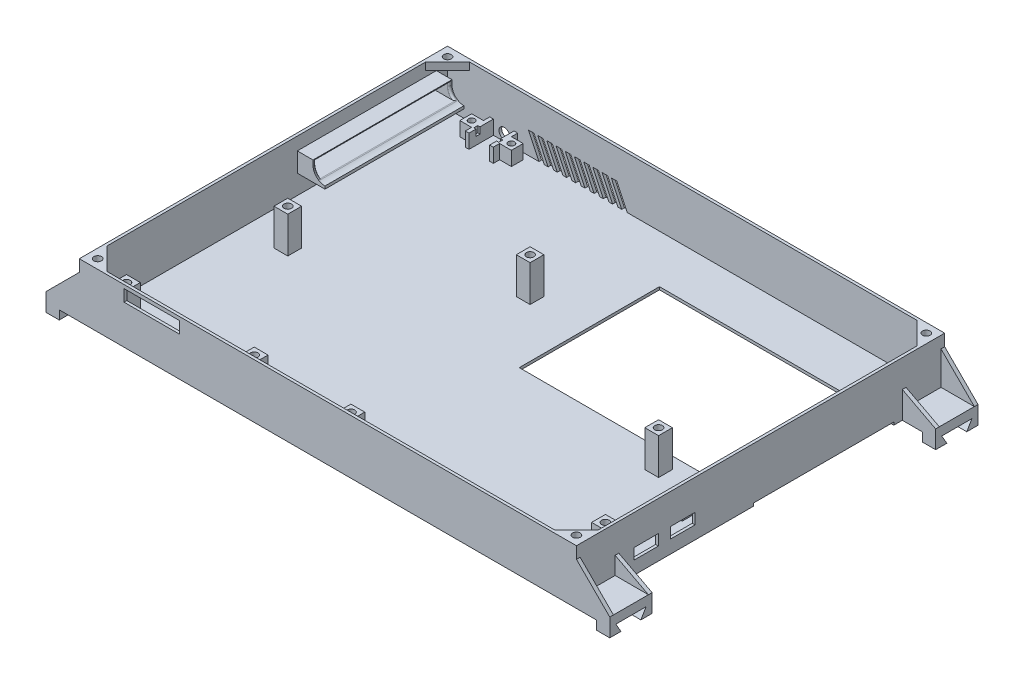
SolidWorks part; units mm, degrees
material "PLA"
ref_plane "Спереди" through (0, 0, 0) normal (0, 0, 1) x (1, 0, 0)
ref_plane "Сверху" through (0, 0, 0) normal (0, 1, 0) x (1, 0, 0)
ref_plane "Справа" through (0, 0, 0) normal (1, 0, 0) x (0, 0, -1)
sketch "Эскиз1" plane through (0, 0, 0) normal (0, 1, 0) x (1, 0, 0)
  line L1 (135, 100) -> (-135, 100)
  line L2 (135, 100) -> (135, -100)
  line L3 (135, -100) -> (-135, -100)
  line L4 (-135, 100) -> (-135, -100)
  line L5 (135, 100) -> (-135, -100) construction
  line L6 (135, -100) -> (-135, 100) construction
  point P0 (0, 0)
  dimension "D1" = 200
  dimension "D2" = 270
extrude "Бобышка-Вытянуть1" add sketch "Эскиз1" along normal blind 1.5
sketch "Эскиз2" plane through (0, 1.5, 0) normal (0, 1, 0) x (1, 0, 0)
  line L0 (133.5, 98.5) -> (-133.5, 98.5)
  line L1 (-133.5, 98.5) -> (-133.5, -98.5)
  line L2 (-133.5, -98.5) -> (-110.7, -98.5)
  line L3 (133.5, -98.5) -> (133.5, 98.5)
  line L4 (-135, 100) -> (-135, -100)
  line L5 (-135, -100) -> (135, -100)
  line L6 (135, -100) -> (135, 100)
  line L7 (135, 100) -> (-135, 100)
  line L8 (-135, 100) -> (-135, -100)
  line L9 (-135, -100) -> (-110.7, -100)
  line L10 (135, -100) -> (135, 100)
  line L11 (135, 100) -> (-135, 100)
  line L12 (-110.7, -98.5) -> (-110.7, -100)
  line L14 (-80.5, -98.5) -> (-80.5, -100)
  line L16 (-80.5, -98.5) -> (133.5, -98.5)
  line L17 (-80.5, -100) -> (135, -100)
  line L18 (-133.5, -98.5) -> (133.5, -98.5) construction
  line L20 (-135, -100) -> (135, -100) construction
  dimension "D3" = 24.3
  dimension "D4" = 54.5
  dimension "D1" = 0
  dimension "D2" = 1.5
extrude "Бобышка-Вытянуть2" add sketch "Эскиз2" along normal offset from surface (28 mm away) 7 offset beyond the face yes
sketch "Эскиз3" plane through (0, 1.5, 0) normal (0, 1, 0) x (1, 0, 0)
  line L1 (-110.7, -98.5) -> (-80.5, -98.5)
  line L2 (-110.7, -98.5) -> (-110.7, -100)
  line L3 (-110.7, -100) -> (-80.5, -100)
  line L4 (-80.5, -98.5) -> (-80.5, -100)
extrude "Бобышка-Вытянуть3" add sketch "Эскиз3" along normal blind 19.7
sketch "Эскиз4" plane through (-110.7, 0, 0) normal (1, 0, 0) x (0, 0, -1)
  line L0 (-100, 29.5) -> (-100, 21.2) construction
  line L1 (-98.5, 29.5) -> (-100, 29.5)
  line L2 (-98.5, 29.5) -> (-98.5, 27.6)
  line L3 (-98.5, 27.6) -> (-100, 27.6)
  line L4 (-100, 29.5) -> (-100, 27.6)
  dimension "D1" = 1.9
extrude "Бобышка-Вытянуть4" add sketch "Эскиз4" along normal up to surface (30.2 mm away) up to face at (-80.5, 25.35, 99.25)
sketch "Эскиз5" plane through (135, 0, 0) normal (1, 0, 0) x (0, 0, -1)
  line L0 (-100, 29.5) -> (-100, 0) construction
  line L1 (-55.55, 13) -> (-68.85, 13)
  line L2 (-55.55, 13) -> (-55.55, 7.1)
  line L3 (-55.55, 7.1) -> (-68.85, 7.1)
  line L4 (-68.85, 13) -> (-68.85, 7.1)
  line L5 (-55.55, 13) -> (-68.85, 7.1) construction
  line L6 (-55.55, 7.1) -> (-68.85, 13) construction
  line L7 (-35.55, 13) -> (-48.85, 13)
  line L8 (-35.55, 13) -> (-35.55, 7.1)
  line L9 (-35.55, 7.1) -> (-48.85, 7.1)
  line L10 (-48.85, 13) -> (-48.85, 7.1)
  line L11 (-35.55, 13) -> (-48.85, 7.1) construction
  line L12 (-35.55, 7.1) -> (-48.85, 13) construction
  line L13 (-100, 0) -> (100, 0) construction
  point P0 (-62.2, 10.05)
  point P5 (-42.2, 10.05)
  dimension "D1" = 13.3
  dimension "D2" = 5.9
  dimension "D3" = 6.7
  dimension "D4" = 31.15
  dimension "D5" = 13
extrude "Вырез-Вытянуть1" cut sketch "Эскиз5" against normal up to surface (1.5 mm away) up to face at (133.5, 15.5, 0)
sketch "Эскиз10" plane through (0, 1.5, 0) normal (0, 1, 0) x (1, 0, 0)
  line L0 (133.5, -14.85) -> (133.5, -98.5) construction
  line L1 (124.175, -24.225) -> (116.675, -24.225)
  line L2 (124.175, -24.225) -> (124.175, -31.725)
  line L3 (124.175, -31.725) -> (116.675, -31.725)
  line L4 (116.675, -24.225) -> (116.675, -31.725)
  line L5 (124.175, -24.225) -> (116.675, -31.725) construction
  line L6 (124.175, -31.725) -> (116.675, -24.225) construction
  line L7 (114.55, -56.3) -> (107.05, -56.3)
  line L8 (114.55, -56.3) -> (114.55, -63.8)
  line L9 (114.55, -63.8) -> (107.05, -63.8)
  line L10 (107.05, -56.3) -> (107.05, -63.8)
  line L11 (114.55, -56.3) -> (107.05, -63.8) construction
  line L12 (114.55, -63.8) -> (107.05, -56.3) construction
  line L13 (115.175, -89.275) -> (107.675, -89.275)
  line L14 (115.175, -89.275) -> (115.175, -96.775)
  line L15 (115.175, -96.775) -> (107.675, -96.775)
  line L16 (107.675, -89.275) -> (107.675, -96.775)
  line L17 (115.175, -89.275) -> (107.675, -96.775) construction
  line L18 (115.175, -96.775) -> (107.675, -89.275) construction
  line L19 (133.5, -98.5) -> (-133.5, -98.5) construction
  point P0 (120.425, -27.975)
  point P5 (110.8, -60.05)
  point P10 (111.425, -93.025)
  dimension "D1" = 13.075
  dimension "D2" = 70.525
  dimension "D3" = 22.7
  dimension "D4" = 38.45
  dimension "D5" = 22.075
  dimension "D6" = 5.475
  dimension "D7" = 7.5
extrude "Бобышка-Вытянуть6" add sketch "Эскиз10" along normal blind 6.9
sketch "Эскиз11" plane through (0, 1.5, 0) normal (0, 1, 0) x (1, 0, 0)
  line L1 (-46.7446, -85.75) -> (-54.2446, -85.75)
  line L2 (-46.7446, -85.75) -> (-46.7446, -93.25)
  line L3 (-46.7446, -93.25) -> (-54.2446, -93.25)
  line L4 (-54.2446, -85.75) -> (-54.2446, -93.25)
  line L5 (-46.7446, -85.75) -> (-54.2446, -93.25) construction
  line L6 (-46.7446, -93.25) -> (-54.2446, -85.75) construction
  line L7 (-19.0224, 28.8491) -> (-26.5224, 28.8491)
  line L8 (-19.0224, 28.8491) -> (-19.0224, 36.3491)
  line L9 (-19.0224, 36.3491) -> (-26.5224, 36.3491)
  line L10 (-26.5224, 28.8491) -> (-26.5224, 36.3491)
  line L11 (-19.0224, 28.8491) -> (-26.5224, 36.3491) construction
  line L12 (-19.0224, 36.3491) -> (-26.5224, 28.8491) construction
  line L13 (-115.5446, -93.8424) -> (-123.0446, -93.8424)
  line L14 (-115.5446, -93.8424) -> (-115.5446, -86.3424)
  line L15 (-115.5446, -86.3424) -> (-123.0446, -86.3424)
  line L16 (-123.0446, -93.8424) -> (-123.0446, -86.3424)
  line L17 (-115.5446, -93.8424) -> (-123.0446, -86.3424) construction
  line L18 (-115.5446, -86.3424) -> (-123.0446, -93.8424) construction
  line L19 (-107.65, -14.1324) -> (-115.15, -14.1324)
  line L20 (-107.65, -14.1324) -> (-107.65, -6.6324)
  line L21 (-107.65, -6.6324) -> (-115.15, -6.6324)
  line L22 (-115.15, -14.1324) -> (-115.15, -6.6324)
  line L23 (-107.65, -14.1324) -> (-115.15, -6.6324) construction
  line L24 (-107.65, -6.6324) -> (-115.15, -14.1324) construction
  line L25 (97.2279, -17.6196) -> (89.7279, -17.6196)
  line L26 (97.2279, -17.6196) -> (97.2279, -10.1196)
  line L27 (97.2279, -10.1196) -> (89.7279, -10.1196)
  line L28 (89.7279, -17.6196) -> (89.7279, -10.1196)
  line L29 (97.2279, -17.6196) -> (89.7279, -10.1196) construction
  line L30 (97.2279, -10.1196) -> (89.7279, -17.6196) construction
  line L31 (94.0554, -99.0196) -> (86.5554, -99.0196)
  line L32 (94.0554, -99.0196) -> (94.0554, -91.5196)
  line L33 (94.0554, -91.5196) -> (86.5554, -91.5196)
  line L34 (86.5554, -99.0196) -> (86.5554, -91.5196)
  line L35 (94.0554, -99.0196) -> (86.5554, -91.5196) construction
  line L36 (94.0554, -91.5196) -> (86.5554, -99.0196) construction
  line L37 (6.3554, -93.8285) -> (-1.1446, -93.8285)
  line L38 (6.3554, -93.8285) -> (6.3554, -86.3285)
  line L39 (6.3554, -86.3285) -> (-1.1446, -86.3285)
  line L40 (-1.1446, -93.8285) -> (-1.1446, -86.3285)
  line L41 (6.3554, -93.8285) -> (-1.1446, -86.3285) construction
  line L42 (6.3554, -86.3285) -> (-1.1446, -93.8285) construction
  line L44 (-133.5, 98.5) -> (133.5, 98.5) construction
  line L45 (-133.5, -98.5) -> (-133.5, 98.5) construction
  line L47 (133.5, -98.5) -> (-133.5, -98.5) construction
  line L48 (133.5, 98.5) -> (133.5, -98.5) construction
  point P0 (-50.4946, -89.5)
  point P5 (-22.7724, 32.5991)
  point P10 (-119.2946, -90.0924)
  point P15 (-111.4, -10.3824)
  point P20 (93.4779, -13.8696)
  point P25 (90.3054, -95.2696)
  point P30 (2.6054, -90.0785)
  dimension "D1" = 7.5
  dimension "D2" = 65.9009
  dimension "D3" = 110.7276
  dimension "D4" = 108.8824
  dimension "D5" = 22.1
  dimension "D6" = 8.4076
  dimension "D7" = 14.2054
  dimension "D8" = 8.4215
  dimension "D9" = 130.8946
  dimension "D10" = 9
  dimension "D11" = 83.0054
  dimension "D12" = 3.2304
  dimension "D13" = 43.1946
  dimension "D14" = 84.6304
  dimension "D15" = 40.0221
extrude "Бобышка-Вытянуть7" add sketch "Эскиз11" along normal blind 19.7
sketch "Эскиз12" plane through (0, 1.5, 0) normal (0, 1, 0) x (1, 0, 0)
  line L1 (135, 72.4) -> (7.7, 72.4)
  line L2 (135, 72.4) -> (135, -3.75)
  line L3 (135, -3.75) -> (7.7, -3.75)
  line L4 (7.7, 72.4) -> (7.7, -3.75)
  line L5 (-133.5, 98.5) -> (133.5, 98.5) construction
  line L6 (135, -100) -> (135, 100) construction
  dimension "D1" = 76.15
  dimension "D2" = 127.3
  dimension "D3" = 26.1
extrude "Вырез-Вытянуть2" cut sketch "Эскиз12" against normal through all
sketch "Эскиз14" plane through (0, 21.2, 0) normal (0, 1, 0) x (1, 0, 0)
  line L0 (-115.15, -6.6324) -> (-107.65, -14.1324) construction
  line L1 (-107.65, -6.6324) -> (-115.15, -14.1324) construction
  line L2 (-19.0224, 36.3491) -> (-26.5224, 28.8491) construction
  line L3 (-26.5224, 36.3491) -> (-19.0224, 28.8491) construction
  line L4 (-123.0446, -86.3424) -> (-115.5446, -93.8424) construction
  line L5 (-115.5446, -86.3424) -> (-123.0446, -93.8424) construction
  line L6 (-54.2446, -85.75) -> (-46.7446, -93.25) construction
  line L7 (-46.7446, -85.75) -> (-54.2446, -93.25) construction
  line L8 (-1.1446, -86.3285) -> (6.3554, -93.8285) construction
  line L9 (6.3554, -86.3285) -> (-1.1446, -93.8285) construction
  line L10 (94.0554, -91.5196) -> (86.5554, -99.0196) construction
  line L11 (94.0554, -91.5196) -> (86.5554, -91.5196) construction
  line L12 (94.0554, -91.5196) -> (94.0554, -99.0196) construction
  line L13 (94.0554, -99.0196) -> (86.5554, -99.0196) construction
  line L14 (86.5554, -91.5196) -> (86.5554, -99.0196) construction
  line L15 (94.0554, -99.0196) -> (86.5554, -91.5196) construction
  line L22 (97.2279, -10.1196) -> (89.7279, -17.6196) construction
  line L23 (97.2279, -17.6196) -> (89.7279, -10.1196) construction
  circle A0 centre (-22.7724, 32.5991) radius 2.05
  circle A1 centre (-111.4, -10.3824) radius 2.05
  circle A2 centre (-119.2946, -90.0924) radius 2.05
  circle A3 centre (-50.4946, -89.5) radius 2.05
  circle A4 centre (2.6054, -90.0785) radius 2.05
  circle A5 centre (90.3054, -95.2696) radius 2.05
  circle A6 centre (93.4779, -13.8696) radius 2.05
  dimension "D1" = 4.1
extrude "Вырез-Вытянуть4" cut sketch "Эскиз14" against normal blind 5
sketch "Эскиз15" plane through (0, 8.4, 0) normal (0, 1, 0) x (1, 0, 0)
  line L0 (124.175, -24.225) -> (116.675, -31.725) construction
  line L1 (116.675, -24.225) -> (124.175, -31.725) construction
  line L2 (107.05, -56.3) -> (114.55, -63.8) construction
  line L3 (114.55, -56.3) -> (107.05, -63.8) construction
  line L4 (107.675, -89.275) -> (115.175, -96.775) construction
  line L5 (115.175, -89.275) -> (107.675, -96.775) construction
  circle A0 centre (111.425, -93.025) radius 2.05
  circle A1 centre (110.8, -60.05) radius 2.05
  circle A2 centre (120.425, -27.975) radius 2.05
  dimension "D1" = 4.1
extrude "Вырез-Вытянуть5" cut sketch "Эскиз15" against normal blind 5
sketch "Эскиз16" plane through (0, 0, -100) normal (0, 0, -1) x (-1, 0, 0)
  line L0 (133.5, 22.5) -> (125, 22.5)
  line L1 (133.5, 29.5) -> (133.5, 1.5) construction
  line L2 (125, 22.5) -> (125, 20)
  line L3 (118.5, 13.5) -> (133.5, 13.5)
  line L4 (133.5, 13.5) -> (133.5, 22.5)
  line L5 (133.5, 1.5) -> (-133.5, 1.5) construction
  arc A0 (125, 20) -> (118.5, 13.5) centre (118.5, 20) cw
  dimension "D3" = 6.5
  dimension "D1" = 8.5
  dimension "D2" = 2.5
  dimension "D4" = 21
  dimension "D5" = 15
extrude "Бобышка-Вытянуть8" add sketch "Эскиз16" against normal blind 75.5 from offset 7.5824 offset against normal yes
sketch "Эскиз18" plane through (0, 0, -16.9176) normal (0, 0, 1) x (1, 0, 0)
  line L0 (-135, 21.5) -> (-125, 21.5)
  line L1 (-135, 29.5) -> (-135, 0) construction
  line L2 (-125, 22.5) -> (-125, 20) construction
  line L3 (-125, 21.5) -> (-125, 20)
  line L4 (-135, 21.5) -> (-135, 14.5)
  line L5 (-135, 14.5) -> (-121.9641, 14.5)
  line L6 (-133.5, 22.5) -> (-125, 22.5) construction
  line L7 (-118.5, 13.5) -> (-133.5, 13.5) construction
  arc A0 (-125, 20) -> (-118.5, 13.5) centre (-118.5, 20) ccw construction
  arc A1 (-125, 20) -> (-121.9641, 14.5) centre (-118.5, 20) ccw
  dimension "D1" = 1
  dimension "D2" = 1
extrude "Вырез-Вытянуть6" cut sketch "Эскиз18" against normal offset from surface (72.5 mm away) 1.5 from offset 1.5 up to face at (-127.3692, 18.1308, -92.4176) offset against normal yes
fillet "Скругление1" radius 1 6 edges at (-125, 20.75, -90.9176) (-125, 20.75, -18.4176) (-124.1906, 16.8589, -90.9176) (-121.9641, 14.5, -54.6676) (-124.1906, 16.8589, -18.4176) (-125, 21.5, -54.6676)
sketch "Эскиз19" plane through (0, 0, -16.9176) normal (0, 0, 1) x (1, 0, 0)
  line L0 (-133.5, 13.5) -> (-133.5, 12)
  line L1 (-133.5, 29.5) -> (-133.5, 1.5) construction
  line L2 (-133.5, 13.5) -> (-118.5, 13.5)
  line L3 (-118.5, 13.5) -> (-133.5, 13.5) construction
  line L4 (-118.5, 13.5) -> (-118.5, 12)
  line L5 (-118.5, 12) -> (-133.5, 12)
  dimension "D1" = 1.5
extrude "Бобышка-Вытянуть9" add sketch "Эскиз19" against normal up to surface (75.5 mm away) up to face at (-127.3692, 18.1308, -92.4176)
sketch "Эскиз20" plane through (0, 0, -100) normal (0, 0, -1) x (-1, 0, 0)
  line L0 (135, 29.5) -> (135, 0) construction
  line L1 (89.5705, 13.5) -> (86.5705, 13.5)
  line L3 (83.9, 1.5) -> (80.9, 1.5)
  line L5 (90.9, 13.5) -> (35.9, 1.5) construction
  line L6 (90.9, 1.5) -> (35.9, 13.5) construction
  line L7 (-135, 0) -> (135, 0) construction
  line L8 (35.9, 1.5) -> (41.5705, 13.5)
  line L9 (44.5705, 13.5) -> (38.9, 1.5)
  line L10 (40.9, 1.5) -> (46.5705, 13.5)
  line L11 (49.5705, 13.5) -> (43.9, 1.5)
  line L12 (45.9, 1.5) -> (51.5705, 13.5)
  line L13 (54.5705, 13.5) -> (48.9, 1.5)
  line L14 (50.9, 1.5) -> (56.5705, 13.5)
  line L15 (59.5705, 13.5) -> (53.9, 1.5)
  line L16 (55.9, 1.5) -> (61.5705, 13.5)
  line L17 (64.5705, 13.5) -> (58.9, 1.5)
  line L18 (60.9, 1.5) -> (66.5705, 13.5)
  line L19 (69.5705, 13.5) -> (63.9, 1.5)
  line L20 (65.9, 1.5) -> (71.5705, 13.5)
  line L21 (74.5705, 13.5) -> (68.9, 1.5)
  line L22 (70.9, 1.5) -> (76.5705, 13.5)
  line L23 (79.5705, 13.5) -> (73.9, 1.5)
  line L24 (75.9, 1.5) -> (81.5705, 13.5)
  line L25 (84.5705, 13.5) -> (78.9, 1.5)
  line L26 (80.9, 1.5) -> (86.5705, 13.5)
  line L27 (89.5705, 13.5) -> (83.9, 1.5)
  line L28 (44.5705, 13.5) -> (41.5705, 13.5)
  line L29 (38.9, 1.5) -> (35.9, 1.5)
  line L30 (43.9, 1.5) -> (40.9, 1.5)
  line L31 (49.5705, 13.5) -> (46.5705, 13.5)
  line L32 (54.5705, 13.5) -> (51.5705, 13.5)
  line L33 (48.9, 1.5) -> (45.9, 1.5)
  line L34 (53.9, 1.5) -> (50.9, 1.5)
  line L35 (59.5705, 13.5) -> (56.5705, 13.5)
  line L36 (58.9, 1.5) -> (55.9, 1.5)
  line L37 (64.5705, 13.5) -> (61.5705, 13.5)
  line L38 (63.9, 1.5) -> (60.9, 1.5)
  line L39 (69.5705, 13.5) -> (66.5705, 13.5)
  line L40 (68.9, 1.5) -> (65.9, 1.5)
  line L41 (74.5705, 13.5) -> (71.5705, 13.5)
  line L42 (73.9, 1.5) -> (70.9, 1.5)
  line L43 (79.5705, 13.5) -> (76.5705, 13.5)
  line L44 (78.9, 1.5) -> (75.9, 1.5)
  line L45 (84.5705, 13.5) -> (81.5705, 13.5)
  line L46 (35.9, 13.5) -> (35.9, 1.5) construction
  line L47 (90.9, 13.5) -> (90.9, 1.5) construction
  point P0 (63.4, 7.5)
  dimension "D1" = 71.6
  dimension "D2" = 1.5
  dimension "D3" = 12
  dimension "D4" = 55
  dimension "D5" = 3
  dimension "D8" = 2
  dimension "D9" = 64.707
  dimension "D6" = 10
extrude "Вырез-Вытянуть7" cut sketch "Эскиз20" against normal up to surface (1.5 mm away) up to face at (0, 15.5, -98.5)
sketch "Эскиз21" plane through (0, 0, -100) normal (0, 0, -1) x (-1, 0, 0)
  line L0 (135, 29.5) -> (135, 0) construction
  line L1 (-135, 0) -> (135, 0) construction
  circle A0 centre (102.7, 5.325) radius 2.9
  dimension "D1" = 5.8
  dimension "D2" = 32.3
  dimension "D3" = 5.325
extrude "Вырез-Вытянуть8" cut sketch "Эскиз21" against normal up to surface (1.5 mm away) up to face at (-57.032, 8.2273, -98.5)
sketch "Эскиз22" plane through (0, 1.5, 0) normal (0, 1, 0) x (1, 0, 0)
  line L0 (-133.5, 98.5) -> (-83.9, 98.5) construction
  line L1 (-108.6, 98.5) -> (-110.6, 98.5)
  line L2 (-108.6, 98.5) -> (-108.6, 85.25)
  line L3 (-108.6, 85.25) -> (-110.6, 85.25)
  line L4 (-110.6, 98.5) -> (-110.6, 85.25)
  line L5 (-133.5, -98.5) -> (-133.5, 98.5) construction
  line L7 (-95.4, 98.5) -> (-97.4, 98.5)
  line L8 (-95.4, 98.5) -> (-95.4, 85.25)
  line L9 (-95.4, 85.25) -> (-97.4, 85.25)
  line L10 (-97.4, 98.5) -> (-97.4, 85.25)
  dimension "D1" = 24.9
  dimension "D2" = 13.25
  dimension "D3" = 2
  dimension "D4" = 36.1
extrude "Бобышка-Вытянуть10" add sketch "Эскиз22" along normal blind 7.65
sketch "Эскиз23" plane through (0, 9.15, 0) normal (0, 1, 0) x (1, 0, 0)
  line L0 (-108.6, 85.25) -> (-108.6, 98.5) construction
  line L1 (-108.6, 91.2) -> (-109.8, 91.2)
  line L2 (-108.6, 91.2) -> (-108.6, 89)
  line L3 (-108.6, 89) -> (-109.8, 89)
  line L4 (-109.8, 91.2) -> (-109.8, 89)
  line L5 (-97.4, 98.5) -> (-97.4, 85.25) construction
  line L6 (-97.4, 91.2) -> (-96.2, 91.2)
  line L7 (-97.4, 91.2) -> (-97.4, 89)
  line L8 (-97.4, 89) -> (-96.2, 89)
  line L9 (-96.2, 91.2) -> (-96.2, 89)
  line L10 (-110.6, 85.25) -> (-108.6, 85.25) construction
  dimension "D1" = 2.2
  dimension "D2" = 1.2
  dimension "D3" = 5.95
extrude "Вырез-Вытянуть9" cut sketch "Эскиз23" against normal blind 3.45
sketch "Эскиз24" plane through (0, 1.5, 0) normal (0, 1, 0) x (1, 0, 0)
  line L0 (-108.6, 91.875) -> (-97.4, 91.875) construction
  line L3 (-103, 91.875) -> (-103, 50091.875) construction
  line L4 (-108.6, 85.25) -> (-108.6, 98.5) construction
  line L5 (-108.6, 98.5) -> (-97.4, 98.5) construction
  line L6 (-110.6, 98.5) -> (-110.6, 85.25) construction
  line L7 (-117, 95.075) -> (-110.6, 95.075)
  line L8 (-117, 95.075) -> (-117, 88.675)
  line L9 (-117, 88.675) -> (-110.6, 88.675)
  line L10 (-110.6, 95.075) -> (-110.6, 88.675)
  line L11 (-117, 95.075) -> (-110.6, 88.675) construction
  line L12 (-117, 88.675) -> (-110.6, 95.075) construction
  line L13 (-89, 88.675) -> (-95.4, 88.675)
  line L14 (-95.4, 95.075) -> (-95.4, 88.675)
  line L15 (-89, 95.075) -> (-95.4, 95.075)
  line L16 (-89, 95.075) -> (-89, 88.675)
  circle A0 centre (-113.8, 91.875) radius 1.7 construction
  point P3 (-108.6, 91.875)
  point P8 (-103, 98.5)
  point P10 (-113.8, 91.875)
  dimension "D1" = 3.4
  dimension "D2" = 1.5
extrude "Бобышка-Вытянуть11" add sketch "Эскиз24" along normal up to surface (7.65 mm away) up to face at (-109.4, 9.15, -90.9875)
sketch "Эскиз25" plane through (0, 9.15, 0) normal (0, 1, 0) x (1, 0, 0)
  line L0 (-117, 95.075) -> (-110.6, 88.675) construction
  line L1 (-110.6, 95.075) -> (-117, 88.675) construction
  line L2 (-95.4, 95.075) -> (-89, 88.675) construction
  line L3 (-89, 95.075) -> (-95.4, 88.675) construction
  circle A0 centre (-113.8, 91.875) radius 1.7
  circle A1 centre (-92.2, 91.875) radius 1.7
  dimension "D1" = 3.4
extrude "Вырез-Вытянуть10" cut sketch "Эскиз25" against normal blind 3
sketch "Эскиз26" plane through (0, 29.5, 0) normal (0, 1, 0) x (1, 0, 0)
  line L0 (0, 0) -> (0, 50000) construction
  line L1 (0, 0) -> (-50000, 0) construction
  line L2 (121.5, 98.5) -> (133.5, 98.5)
  line L3 (-35.9, 98.5) -> (133.5, 98.5) construction
  line L4 (133.5, 98.5) -> (133.5, 86.5)
  line L5 (133.5, 98.5) -> (133.5, -98.5) construction
  line L6 (133.5, 86.5) -> (121.5, 98.5)
  line L7 (133.5, 98.5) -> (127.5, 92.5) construction
  line L8 (133.5, -98.5) -> (133.5, -86.5)
  line L9 (121.5, -98.5) -> (133.5, -98.5)
  line L10 (133.5, -86.5) -> (121.5, -98.5)
  line L11 (-121.5, -98.5) -> (-133.5, -98.5)
  line L12 (-133.5, -86.5) -> (-121.5, -98.5)
  line L13 (-133.5, -98.5) -> (-133.5, -86.5)
  line L14 (-133.5, 98.5) -> (-133.5, 86.5)
  line L15 (-121.5, 98.5) -> (-133.5, 98.5)
  line L16 (-133.5, 86.5) -> (-121.5, 98.5)
  circle A0 centre (130.0102, 95.0102) radius 2.05 construction
  dimension "D1" = 4.1
  dimension "D3" = 1.5
  dimension "D4" = 1.4398
  dimension "D2" = 12
extrude "Бобышка-Вытянуть12" add sketch "Эскиз26" against normal blind 4
sketch "Эскиз27" plane through (0, 29.5, 0) normal (0, 1, 0) x (1, 0, 0)
  line L0 (0, 0) -> (0, 50000) construction
  line L1 (0, 0) -> (-50000, 0) construction
  line L2 (135, 100) -> (127.5, 92.5) construction
  line L3 (121.5, 98.5) -> (133.5, 86.5) construction
  circle A0 centre (130.0102, 95.0102) radius 2.05
  circle A1 centre (130.0102, -95.0102) radius 2.05
  circle A2 centre (-130.0102, -95.0102) radius 2.05
  circle A3 centre (-130.0102, 95.0102) radius 2.05
  dimension "D1" = 4.1
  dimension "D2" = 1.5
extrude "Вырез-Вытянуть11" cut sketch "Эскиз27" against normal up to surface (4 mm away) up to face at (129.5, 25.5, -94.5)
sketch "Эскиз29" plane through (135, 0, 0) normal (1, 0, 0) x (0, 0, -1)
  line L0 (0, 29.5) -> (0, -49970.5) construction
  line L2 (100, 0) -> (77, 0)
  line L3 (100, 0) -> (100, 5)
  line L4 (100, 5) -> (77, 5)
  line L5 (77, 0) -> (77, 5)
  line L9 (-100, 29.5) -> (100, 29.5) construction
  line L10 (-100, 5) -> (-77, 5)
  line L11 (-77, 0) -> (-77, 5)
  line L12 (-100, 0) -> (-77, 0)
  line L13 (-100, 0) -> (-100, 5)
  point P14 (0, 29.5)
  dimension "D1" = 23
  dimension "D2" = 5
extrude "Бобышка-Вытянуть13" add sketch "Эскиз29" along normal blind 18.1
sketch "Эскиз30" plane through (153.1, 0, 0) normal (1, 0, 0) x (0, 0, -1)
  line L0 (0, 29.5) -> (0, -49970.5) construction
  line L1 (-100, 29.5) -> (100, 29.5) construction
  line L2 (96.7, 0) -> (100, 0)
  line L3 (77, 0) -> (100, 0) construction
  line L4 (100, 0) -> (100, -4.8)
  line L5 (100, -4.8) -> (93.9, -4.8)
  line L6 (93.9, -4.8) -> (96.7, 0)
  line L7 (80.3, 0) -> (77, 0)
  line L8 (77, 0) -> (77, -4.8)
  line L9 (77, -4.8) -> (83.1, -4.8)
  line L10 (83.1, -4.8) -> (80.3, 0)
  line L11 (100, 0) -> (100, 5) construction
  line L13 (-77, -4.8) -> (-83.1, -4.8)
  line L14 (-77, 0) -> (-77, -4.8)
  line L15 (-80.3, 0) -> (-77, 0)
  line L16 (-83.1, -4.8) -> (-80.3, 0)
  line L17 (-100, -4.8) -> (-93.9, -4.8)
  line L18 (-100, 0) -> (-100, -4.8)
  line L19 (-96.7, 0) -> (-100, 0)
  line L20 (-93.9, -4.8) -> (-96.7, 0)
  point P4 (0, 29.5)
  dimension "D1" = 4.8
  dimension "D2" = 6.1
  dimension "D3" = 3.3
extrude "Бобышка-Вытянуть14" add sketch "Эскиз30" against normal blind 7.2
mirror "Зеркальное отражение3" about plane through (0, 0, 0) normal (1, 0, 0) of "Бобышка-Вытянуть13"
mirror "Зеркальное отражение4" about plane through (0, 0, 0) normal (1, 0, 0) of "Бобышка-Вытянуть14"
sketch "Эскиз35" plane through (0, 0, -100) normal (0, 0, -1) x (-1, 0, 0)
  line L0 (153.1, 5) -> (135, 23.1)
  line L1 (135, 29.5) -> (135, 5) construction
  line L2 (135, 23.1) -> (135, 5)
  line L3 (135, 5) -> (153.1, 5)
  dimension "D1" = 45
extrude "Бобышка-Вытянуть15" add sketch "Эскиз35" against normal blind 2
sketch "Эскиз36" plane through (0, 0, -77) normal (0, 0, 1) x (1, 0, 0)
  line L0 (-153.1, 5) -> (-135, 14.5)
  line L1 (-135, 29.5) -> (-135, 5) construction
  line L2 (-135, 14.5) -> (-135, 5)
  line L3 (-135, 5) -> (-153.1, 5)
extrude "Бобышка-Вытянуть16" add sketch "Эскиз36" against normal blind 2
mirror "Зеркальное отражение6" about plane through (0, 0, 0) normal (0, 0, 1) of "Бобышка-Вытянуть16", "Бобышка-Вытянуть15"
mirror "Зеркальное отражение7" about plane through (0, 0, 0) normal (1, 0, 0) of "Зеркальное отражение6"
